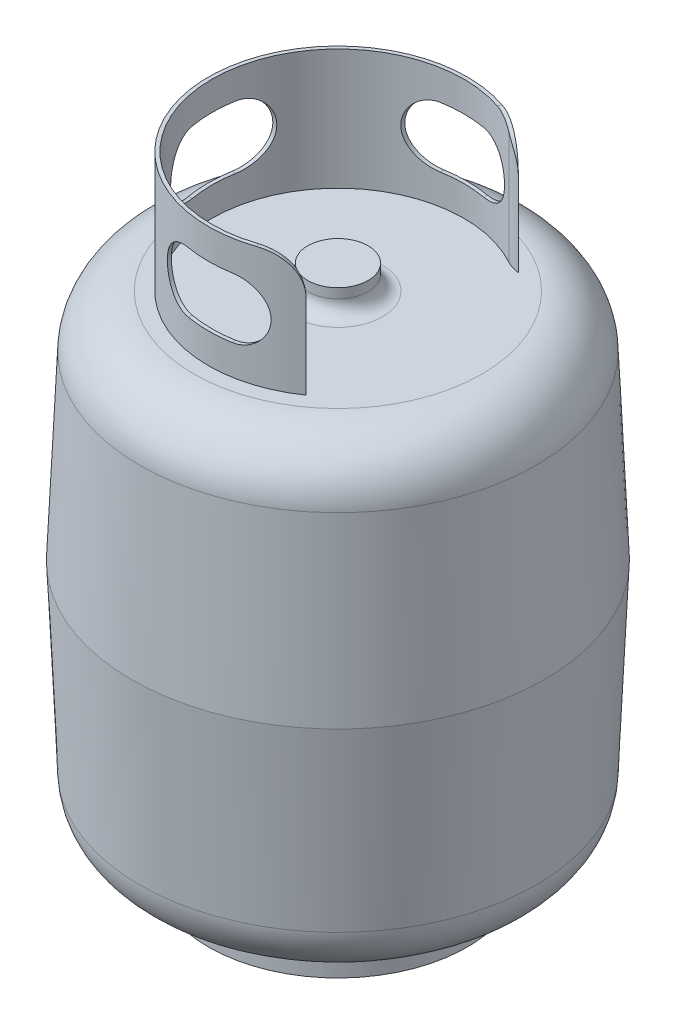
SolidWorks part; units mm, degrees
material "1060 Alloy"
ref_plane "Front Plane" through (0, 0, 0) normal (0, 0, 1) x (1, 0, 0)
ref_plane "Top Plane" through (0, 0, 0) normal (0, 1, 0) x (1, 0, 0)
ref_plane "Right Plane" through (0, 0, 0) normal (1, 0, 0) x (0, 0, -1)
sketch "Sketch1" plane through (0, 0, 0) normal (0, 0, 1) x (1, 0, 0)
  line L0 (0, 0) -> (119.4219, 0)
  line L1 (164.379, 43.0371) -> (170.9593, 193.75)
  line L2 (170.9593, 193.75) -> (164.379, 344.4629)
  line L3 (119.4219, 387.5) -> (37, 387.5)
  line L4 (0, 530.7448) -> (0, 0) construction
  line L5 (25, 399.5) -> (25, 407.5)
  line L6 (25, 407.5) -> (0, 407.5)
  line L7 (0, 4) -> (119.4219, 4)
  line L8 (160.3828, 43.2116) -> (166.9555, 193.75)
  line L9 (166.9555, 193.75) -> (160.3828, 344.2884)
  line L10 (119.4219, 383.5) -> (37, 383.5)
  line L11 (21, 399.5) -> (21, 403.5)
  line L12 (21, 403.5) -> (0, 403.5)
  line L13 (0, 407.5) -> (0, 403.5)
  line L14 (0, 4) -> (0, 0)
  arc A0 (164.379, 344.4629) -> (119.4219, 387.5) centre (119.4219, 342.5) ccw
  arc A1 (119.4219, 0) -> (164.379, 43.0371) centre (119.4219, 45) ccw
  arc A2 (25, 399.5) -> (37, 387.5) centre (37, 399.5) ccw
  arc A3 (119.4219, 4) -> (160.3828, 43.2116) centre (119.4219, 45) ccw
  arc A4 (160.3828, 344.2884) -> (119.4219, 383.5) centre (119.4219, 342.5) ccw
  arc A5 (21, 399.5) -> (37, 383.5) centre (37, 399.5) ccw
  point P11 (162.5, 387.5)
  point P14 (162.5, 0)
  dimension "D8" = 45
  dimension "D9" = 45
  dimension "D1" = 162.5
  dimension "D2" = 387.5
  dimension "D4" = 92.5
  dimension "D3" = 25
  dimension "D6" = 162.5
  dimension "D7" = 92.5
  dimension "D10" = 12
  dimension "D5" = 4
revolve "Revolve1" add sketch "Sketch1" angle 360 about L4
sketch "Sketch2" plane through (0, 387.5, 0) normal (0, 1, 0) x (1, 0, 0)
  circle A0 centre (0, 0) radius 21
  dimension "D1" = 42
sketch "Sketch7" plane through (0, 0, 0) normal (0, -1, 0) x (1, 0, 0)
  circle A0 centre (0, 0) radius 107.4219
  circle A1 centre (0, 0) radius 119.4219
  circle A2 centre (0, 0) radius 119.4219 construction
  circle A3 centre (0, 0) radius 104.4219
  dimension "D2" = 12
  dimension "D1" = 0
  dimension "D3" = 3
extrude "Boss-Extrude2" add sketch "Sketch7" along normal blind 30 contours A0
sketch "Sketch12" plane through (0, 0, 0) normal (0, -1, 0) x (1, 0, 0)
  circle A0 centre (0, 0) radius 104.4219
  circle A1 centre (0, 0) radius 107.4219 construction
  dimension "D1" = 3
extrude "Cut-Extrude4" cut sketch "Sketch12" against normal blind 30
sketch "Sketch14" plane through (0, -30, 0) normal (0, -1, 0) x (1, 0, 0)
  circle A1 centre (0, 0) radius 95.4219
extrude "Cut-Extrude9" cut sketch "Sketch14" against normal blind 20 contours A1
sketch "Sketch15" plane through (0, -30, 0) normal (0, -1, 0) x (1, 0, 0)
  circle A0 centre (0, 0) radius 104.4219
  circle A1 centre (0, 0) radius 107.4219 construction
  dimension "D1" = 3
extrude "Cut-Extrude10" cut sketch "Sketch15" against normal blind 20
sketch "Sketch16" plane through (0, 387.5, 0) normal (0, 1, 0) x (1, 0, 0)
  line L0 (0, 0) -> (0, 107.4219) construction
  line L1 (0, 0) -> (107.4219, 0) construction
  line L2 (0, 0) -> (0, -119.4219) construction
  line L3 (0, 0) -> (74.5798, 106.511) construction
  line L4 (0, 0) -> (76.3589, -109.0518) construction
  line L5 (59.8939, 85.5374) -> (61.6147, 87.9948)
  line L6 (59.8939, -85.5374) -> (61.6147, -87.9948)
  arc A0 (61.6147, 87.9948) -> (61.6147, -87.9948) centre (0, 0) ccw
  circle A1 centre (0, 0) radius 119.4219 construction
  arc A2 (59.8939, 85.5374) -> (59.8939, -85.5374) centre (0, 0) ccw
  circle A3 centre (0, 0) radius 104.4219 construction
  circle A4 centre (0, 0) radius 107.4219 construction
  dimension "D1" = 12
  dimension "D3" = 55
  dimension "D4" = 55
  dimension "D2" = 3
extrude "Boss-Extrude3" add sketch "Sketch16" along normal blind 100
fillet "Fillet2" radius 30 2 edges at (60.7543, 487.5, -86.7661) (59.8939, 437.5, -85.5374)
fillet "Fillet3" radius 30 2 edges at (60.7543, 487.5, 86.7661) (59.8939, 437.5, 85.5374)
sketch "Sketch17" plane through (0, 0, 0) normal (0, 0, 1) x (1, 0, 0)
  line L0 (0, 0) -> (0, 437.5) construction
  line L1 (119.4219, 387.5) -> (-119.4219, 387.5) construction
  line L2 (119.4219, 387.5) -> (-119.4219, 387.5)
  line L3 (-18, 437.5) -> (18, 437.5) construction
  line L4 (-18, 462.5) -> (18, 462.5)
  line L5 (-18, 412.5) -> (18, 412.5)
  arc A0 (-18, 462.5) -> (-18, 412.5) centre (-18, 437.5) ccw
  arc A1 (18, 412.5) -> (18, 462.5) centre (18, 437.5) ccw
  point P7 (0, 437.5)
  dimension "D3" = 25
  dimension "D1" = 50
  dimension "D2" = 36
extrude "Cut-Extrude11" cut sketch "Sketch17" against normal through all both and the other way through all contours A0 L5 A1 L4
sketch "Sketch18" plane through (0, 0, 0) normal (1, 0, 0) x (0, 0, -1)
  line L0 (0, 0) -> (0, 437.5) construction
  line L1 (104.4219, 387.5) -> (-104.4219, 387.5) construction
  line L2 (104.4219, 387.5) -> (-104.4219, 387.5)
  line L3 (-18, 437.5) -> (18, 437.5) construction
  line L4 (-18, 463.5) -> (18, 463.5)
  line L5 (-18, 411.5) -> (18, 411.5)
  arc A0 (-18, 463.5) -> (-18, 411.5) centre (-18, 437.5) ccw
  arc A1 (18, 411.5) -> (18, 463.5) centre (18, 437.5) ccw
  point P7 (0, 437.5)
  dimension "D3" = 26
  dimension "D1" = 50
  dimension "D2" = 36
extrude "Cut-Extrude12" cut sketch "Sketch18" against normal through all both and the other way through all contours A1 L4 A0 L5
equation "\"A\"= 325.00mm"
equation "\"B\"= 387.50mm"
equation "\"D1@Sketch1\"=\"A\" / 2"
equation "\"D2@Sketch1\"=\"B\""
